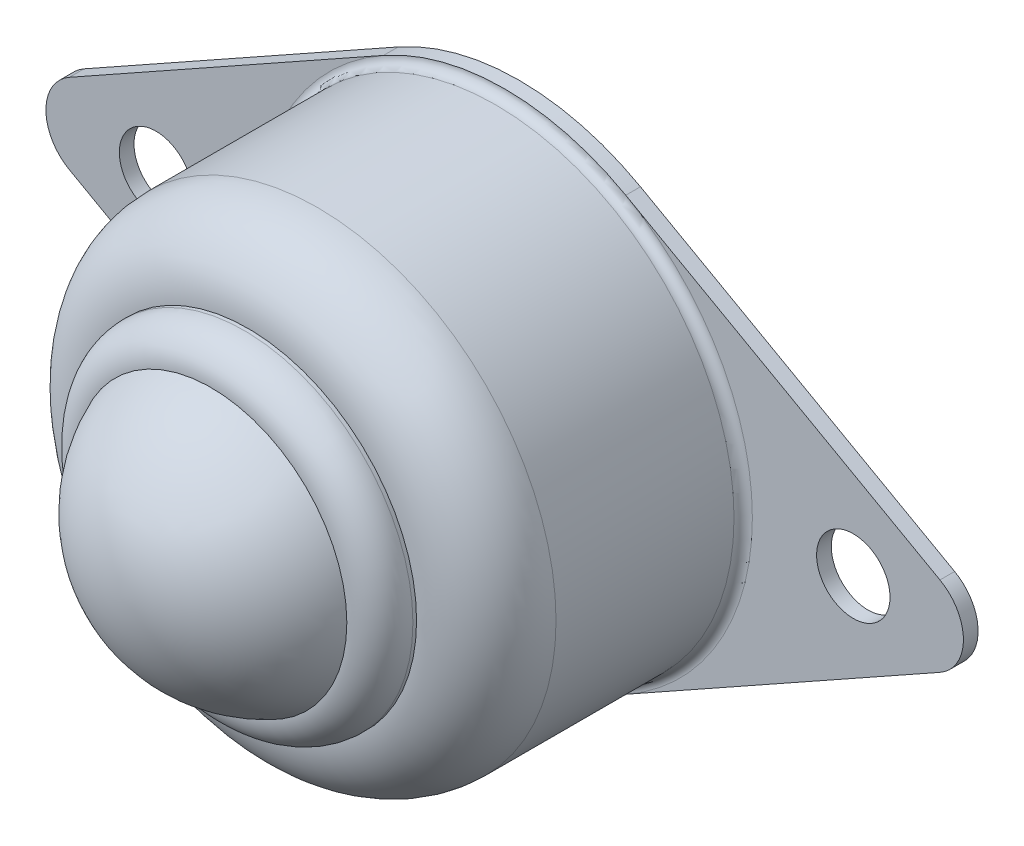
SolidWorks part; units mm, degrees
ref_plane "Alzado" through (0, 0, 0) normal (0, 0, 1) x (1, 0, 0)
ref_plane "Planta" through (0, 0, 0) normal (0, 1, 0) x (1, 0, 0)
ref_plane "Vista lateral" through (0, 0, 0) normal (1, 0, 0) x (0, 0, -1)
sketch "Croquis1" plane through (0, 0, 0) normal (0, 0, 1) x (1, 0, 0)
  line L1 (33, 0) -> (-33, 0) construction
  line L2 (23.7222, 2.1809) -> (6.6, 11.7767)
  line L4 (23.7222, -2.1809) -> (6.6, -11.7767)
  line L6 (-23.7222, 2.1809) -> (-6.6, 11.7767)
  line L9 (-23.7222, -2.1809) -> (-6.6, -11.7767)
  arc A0 (6.6, 11.7767) -> (-6.6, 11.7767) centre (0, 0) ccw
  arc A1 (-23.7222, 2.1809) -> (-23.7222, -2.1809) centre (-22.5, 0) ccw
  arc A2 (23.7222, -2.1809) -> (23.7222, 2.1809) centre (22.5, 0) ccw
  arc A3 (-6.6, -11.7767) -> (6.6, -11.7767) centre (0, 0) ccw
  point P3 (-25, 0)
  point P4 (25, 0)
  point P7 (23.7222, 2.1809)
  point P9 (23.7222, -2.1809)
  dimension "D1" = 27
  dimension "D4" = 5
  dimension "D5" = 5
  dimension "D6" = 1.2778
  dimension "D2" = 25
  dimension "D3" = 25
  dimension "D7" = 1.2778
extrude "Saliente-Extruir1" add sketch "Croquis1" along normal blind 0.8
sketch "Croquis2" plane through (0, 0, 0.8) normal (0, 0, 1) x (1, 0, 0)
  line L0 (0.44, 0) -> (-0.44, 0) construction
  circle A0 centre (-19, 0) radius 2
  circle A1 centre (19, 0) radius 2
  dimension "D1" = 4
  dimension "D2" = 4
  dimension "D3" = 19
  dimension "D4" = 19
extrude "Cortar-Extruir1" cut sketch "Croquis2" against normal blind 10.8
sketch "Croquis3" plane through (0, 0, 0.8) normal (0, 0, 1) x (1, 0, 0)
  circle A0 centre (0, 0) radius 13
  dimension "D1" = 26
extrude "Saliente-Extruir2" add sketch "Croquis3" along normal blind 14
fillet "Redondeo1" radius 3.8 1 edges at (13, 0, 14.8) type face fillet first side face at (13, 0, 14.8) second side face at (13, 0, 14.8)
sketch "Croquis4" plane through (0, 0, 14.8) normal (0, 0, 1) x (1, 0, 0)
  circle A1 centre (0, 0) radius 9.2
extrude "Saliente-Extruir3" add sketch "Croquis4" along normal blind 2
fillet "Redondeo2" radius 1.8 1 edges at (9.2, 0, 16.8) type face fillet first side face at (9.2, 0, 16.8) second side face at (9.2, 0, 16.8)
dome "Cúpula2" faces to dome 1 distance 5 reverse direction no elliptical dome no face at (7.4, 0, 16.8) parameters "D1"=5
fillet "Redondeo3" radius 0.5 1 edges at (13, 0, 0.8) type face fillet first side face at (13, 0, 0.8) second side face at (13, 0, 11)
